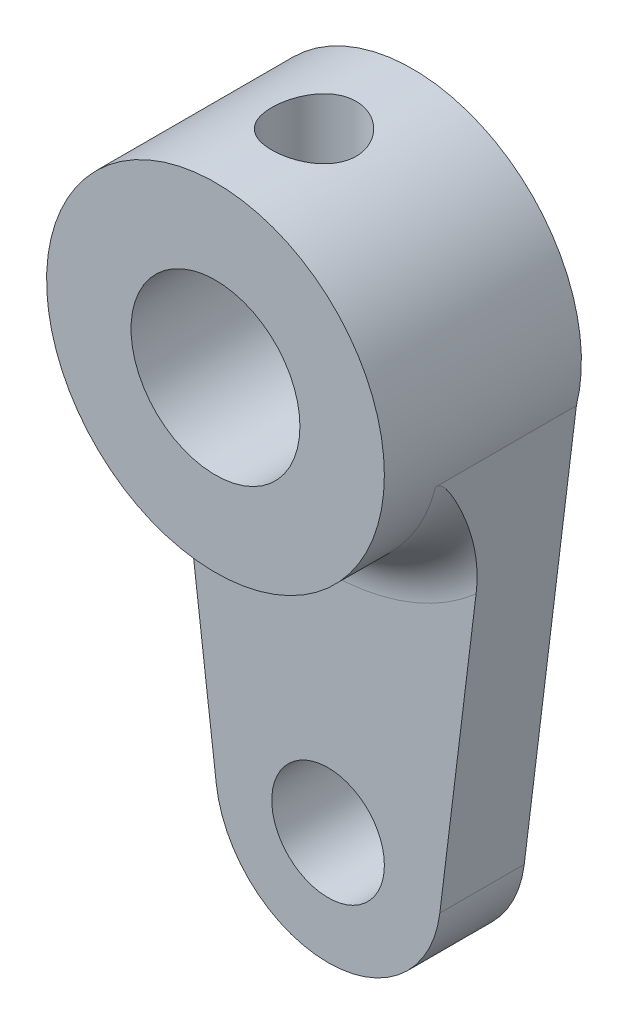
SolidWorks part; units mm, degrees
note: The reader was unsure of these and kept them because the rebuilt part matched: shared geometry of "Sketch1<4>", "Sketch1<5>".
ref_plane "Front Plane" through (0, 0, 0) normal (0, 0, 1) x (1, 0, 0)
ref_plane "Top Plane" through (0, 0, 0) normal (0, 1, 0) x (1, 0, 0)
ref_plane "Right Plane" through (0, 0, 0) normal (1, 0, 0) x (0, 0, -1)
sketch "Sketch1" plane through (0, 0, 0) normal (0, 0, 1) x (1, 0, 0)
  line L0 (6, 0) -> (3.97, -16.4888)
  line L1 (-3.97, -16.4888) -> (-6, 0)
  circle A0 centre (0, 0) radius 6
  circle A1 centre (0, 0) radius 3
  arc A2 (3.97, -16.4888) -> (-3.97, -16.4888) centre (0, -16) cw
  circle A3 centre (0, -16) radius 2
  dimension "D1" = 12
  dimension "D2" = 6
  dimension "D4" = 4
  dimension "D5" = 4
  dimension "D3" = 16
extrude "Boss-Extrude2" add sketch "Sketch1" along normal blind 7 contours A0
extrude "Boss-Extrude3" add sketch "Sketch1<4>" along normal blind 3 contours A2 L0 A0 L1 A3
sketch "Sketch1<4>" plane through (0, 0, 0) normal (0, 0, 1) x (1, 0, 0) same geometry as "Sketch1"
extrude "Cut-Extrude1" cut sketch "Sketch1<5>" along normal through all contours A1
sketch "Sketch1<5>" plane through (0, 0, 0) normal (0, 0, 1) x (1, 0, 0) same geometry as "Sketch1"
fillet "Fillet5" radius 2 1 edges at (0, -6, 3)
sketch "Sketch6" plane through (0, 0, 0) normal (0, 1, 0) x (1, 0, 0)
  line L0 (0, 0) -> (0, -7) construction
  line L1 (-6, -7) -> (6, -7) construction
sketch "Sketch11" plane through (0, 0, 0) normal (0, 0, -1) x (-1, 0, 0)
  line L0 (-6, 7) -> (6, 7)
  point P2 (0, 7)
  dimension "D1" = 7
  dimension "D2" = 12
surface "Surface-Extrude1" sketch "Sketch11" parameters "D1"=7
sketch "Sketch15" plane through (0, 7, 0) normal (0, 1, 0) x (1, 0, 0)
  line L0 (0, 0) -> (0, -7) construction
  point P0 (0, -3.5)
sketch "Sketch18" plane through (0, 7, 0) normal (0, 1, 0) x (1, 0, 0)
  point P0 (0, -3.5)
  dimension "D1" = 3.5
hole_wizard "M3 Tapped Hole2" positions "Sketch18" profile "Sketch17" tap size "M3" standard "ISO"
sketch "Sketch17" plane through (0, 7, 3.5) normal (1, 0, 0) x (0, 0, 1)
  line L0 (0, 0) -> (0, 9.4013)
  line L1 (0, 9.4013) -> (1.5, 8.5)
  line L2 (1.5, 8.5) -> (1.5, 0)
  line L5 (1.5, 0) -> (0, 0)
  line L10 (0, 9.4013) -> (-1.5, 8.5) construction
  line L11 (0, -6.35) -> (0, 107.95) construction
  dimension "Tap Drill Dia." = 3
  dimension "Tap Drill Depth" = 8.5
  dimension "Drill Angle" = 118
cosmetic thread "Hole Thread2" parameters "D1"=8, "D2"=3
